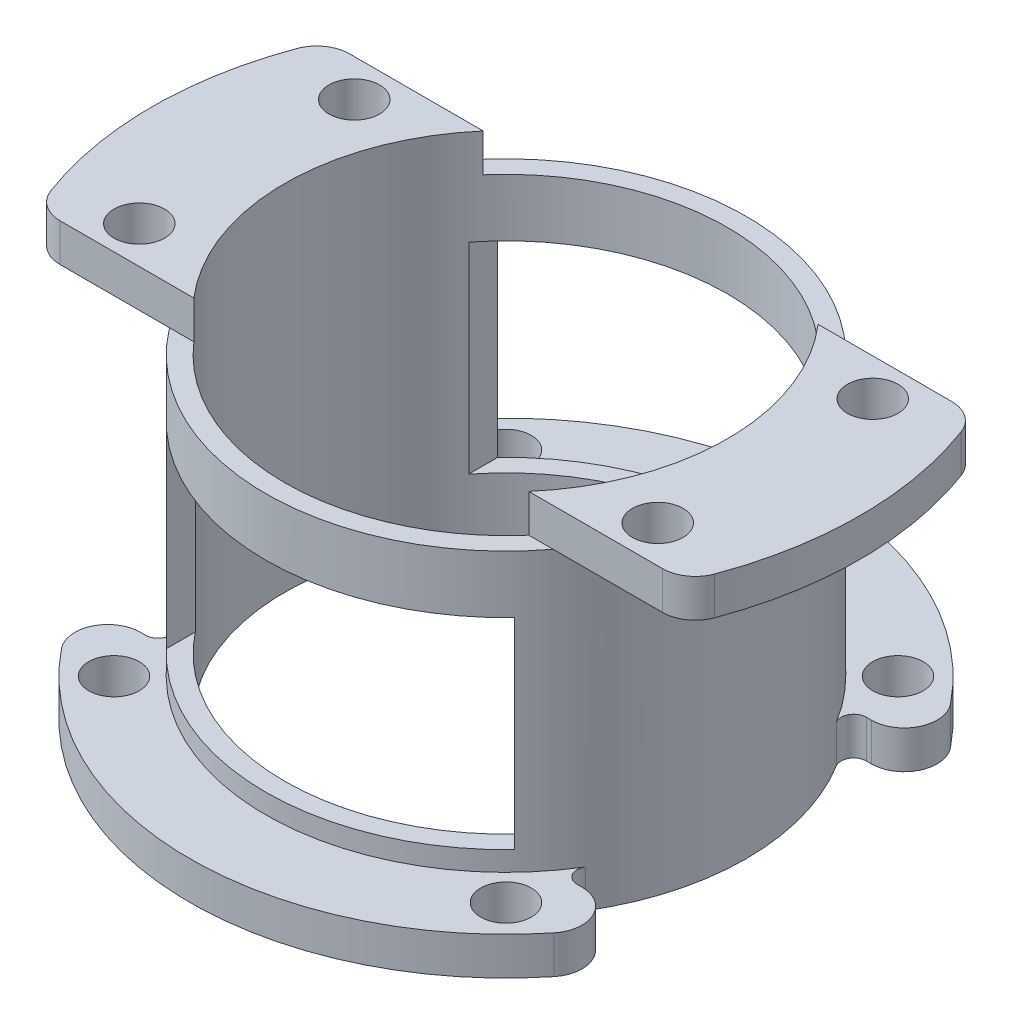
SolidWorks part; units mm, degrees
ref_plane "前视基准面" through (0, 0, 0) normal (0, 0, 1) x (1, 0, 0)
ref_plane "上视基准面" through (0, 0, 0) normal (0, 1, 0) x (1, 0, 0)
ref_plane "右视基准面" through (0, 0, 0) normal (1, 0, 0) x (0, 0, -1)
sketch "草图1" plane through (0, 0, 0) normal (0, 1, 0) x (1, 0, 0)
  circle A0 centre (0, 0) radius 25
  dimension "D1" = 50
extrude "凸台-拉伸1" add sketch "草图1" along normal blind 3 contours A0
sketch "草图2" plane through (0, 0, 0) normal (0, 1, 0) x (1, 0, 0)
  line L1 (-15.5, 15.5) -> (15.5, 15.5)
  line L2 (-15.5, 15.5) -> (-15.5, -15.5)
  line L3 (-15.5, -15.5) -> (15.5, -15.5)
  line L4 (15.5, 15.5) -> (15.5, -15.5)
  line L5 (0, -15.5) -> (0, 15.5) construction
  line L6 (-15.5, 0) -> (15.5, 0) construction
  point P0 (0, 0)
  dimension "D1" = 31
  dimension "D2" = 31
sketch "草图13" plane through (0, 3, 0) normal (0, 1, 0) x (1, 0, 0)
  circle A0 centre (0, 0) radius 19
  dimension "D1" = 38
extrude "凸台-拉伸3" add sketch "草图13" along normal blind 22
sketch "草图6" plane through (0, 25, 0) normal (0, 1, 0) x (1, 0, 0)
  circle A0 centre (0, 0) radius 28
  dimension "D1" = 56
extrude "凸台-拉伸2" add sketch "草图6" along normal blind 3 contours A0
sketch "草图5" plane through (0, 28, 0) normal (0, 1, 0) x (1, 0, 0)
  line L0 (-15.5, 0) -> (15.5, 0) construction
  circle A0 centre (0, 0) radius 17.5
  dimension "D1" = 35
hole_wizard "大小mm 暗销孔2" positions "草图7" profile "草图8" hole size "Ø4.0" standard "GB" end condition up to next
sketch "草图7" plane through (0, 0, 0) normal (0, -1, 0) x (-1, 0, 0)
  point P0 (-15.5, 15.5)
  point P3 (15.5, 15.5)
  point P6 (15.5, -15.5)
  point P9 (-15.5, -15.5)
sketch "草图8" plane through (15.5, 0, -15.5) normal (1, 0, 0) x (0, 0, -1)
  line L0 (0, 0) -> (0, 3)
  line L1 (0, 3) -> (2, 3)
  line L2 (2, 3) -> (2, 0)
  line L5 (2, 0) -> (0, 0)
  line L11 (0, -6.35) -> (0, 107.95) construction
  dimension "通孔孔直径" = 4
  dimension "通孔孔深度" = 3
extrude "切除-拉伸2" cut sketch "草图5" against normal through all
sketch "草图9" plane through (0, 28, 0) normal (0, 1, 0) x (1, 0, 0)
  line L0 (-28, 0) -> (28, 0) construction
  line L3 (0, -28) -> (0, 28) construction
  circle A0 centre (0, 0) radius 28 construction
  point P0 (-22, 0)
  point P3 (0, 0)
  point P4 (22, 0)
  point P10 (0, 0)
  dimension "D1" = 44
sketch "草图17" plane through (0, 28, 0) normal (0, 1, 0) x (1, 0, 0)
  circle A0 centre (-20.5, -8.5) radius 2
  circle A1 centre (-20.5, 8.5) radius 2
  circle A2 centre (20.5, 8.5) radius 2
  circle A3 centre (20.5, -8.5) radius 2
  dimension "D1" = 4
  dimension "D2" = 4
  dimension "D3" = 4
  dimension "D4" = 4
extrude "切除-拉伸7" cut sketch "草图17" against normal up to next
sketch "草图12" plane through (0, 0, 0) normal (0, -1, 0) x (1, 0, 0)
  line L2 (-21, 21) -> (21, 21)
  line L3 (-21, 21) -> (-21, -21)
  line L4 (-21, -21) -> (21, -21)
  line L5 (21, 21) -> (21, -21)
  line L6 (0, -21) -> (0, 21) construction
  line L7 (-21, 0) -> (21, 0) construction
  point P2 (0, 0)
  dimension "D1" = 42
  dimension "D2" = 42
sketch "草图14" plane through (0, 28, 0) normal (0, 1, 0) x (1, 0, 0)
  line L0 (0, 0) -> (20.7735, 0) construction
  line L1 (-30.3012, -11.441) -> (34.2841, -11.441)
  line L2 (-30.3012, -11.441) -> (-30.3012, -31.0868)
  line L3 (-30.3012, -31.0868) -> (34.2841, -31.0868)
  line L4 (34.2841, -11.441) -> (34.2841, -31.0868)
  line L5 (-26.084, 30.1059) -> (35.6117, 30.1059)
  line L6 (-26.084, 30.1059) -> (-26.084, 11.441)
  line L7 (-26.084, 11.441) -> (35.6117, 11.441)
  line L8 (35.6117, 30.1059) -> (35.6117, 11.441)
extrude "切除-拉伸4" cut sketch "草图14" against normal up to surface (3 mm away) up to face at (20.5, 25, 10.5)
sketch "草图15" plane through (0, 0, 0) normal (0, -1, 0) x (1, 0, 0)
  line L0 (-25.5559, 11.441) -> (-15.1691, 11.441)
  line L1 (0, 0) -> (0, 9.2092)
  line L2 (25.5559, 11.441) -> (15.1691, 11.441)
  line L3 (0, 0) -> (4.0327, 0)
  line L4 (25.5559, -11.441) -> (15.1691, -11.441)
  line L5 (-25.5559, -11.441) -> (-15.1691, -11.441)
  arc A2 (-25.5559, 11.441) -> (-25.5559, -11.441) centre (0, 0) ccw
  arc A3 (15.1691, -11.441) -> (15.1691, 11.441) centre (0, 0) ccw
  arc A4 (25.5559, 11.441) -> (25.5559, -11.441) centre (0, 0) cw
  arc A6 (-15.1691, 11.441) -> (-15.1691, -11.441) centre (0, 0) ccw
  circle M4 centre (0, 0) radius 17.5
  circle M8 centre (0, 0) radius 25
extrude "切除-拉伸5" cut sketch "草图15" against normal up to surface (3 mm away) contours L5 L0 M8 M4 | L4 L2 M8 M4 region at (-20.892, 0, 0) region at (20.892, 0, 0) up to face at (15.5, 3, -13.5)
fillet "圆角1" radius 2.6 8 edges at (-22.2284, 1.5, 11.441) (-22.2284, 1.5, -11.441) (22.2284, 1.5, -11.441) (22.2284, 1.5, 11.441) (-25.5559, 26.5, 11.441) (-25.5559, 26.5, -11.441) (25.5559, 26.5, 11.441) (25.5559, 26.5, -11.441)
fillet "圆角2" radius 1 4 edges at (-15.1691, 1.5, -11.441) (-15.1691, 1.5, 11.441) (15.1691, 1.5, -11.441) (15.1691, 1.5, 11.441)
sketch "草图16" plane through (0, 0, 0) normal (0, 0, 1) x (1, 0, 0)
  line L1 (-13.7591, 20.4443) -> (13.7591, 20.4443)
  line L2 (-13.7591, 20.4443) -> (-13.7591, 4.5557)
  line L3 (-13.7591, 4.5557) -> (13.7591, 4.5557)
  line L4 (13.7591, 20.4443) -> (13.7591, 4.5557)
  line L5 (0, 4.5557) -> (0, 20.4443) construction
  line L6 (-13.7591, 12.5) -> (13.7591, 12.5) construction
  point P0 (0, 12.5)
extrude "切除-拉伸6" cut sketch "草图16" against normal through all both and the other way through all
